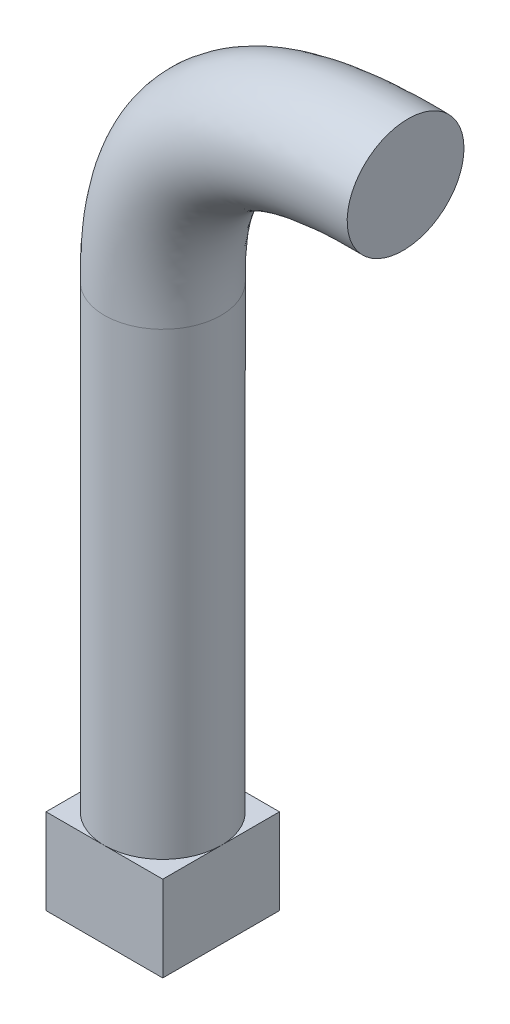
SolidWorks part; units mm, degrees
ref_plane "Front Plane" through (0, 0, 0) normal (0, 0, 1) x (1, 0, 0)
ref_plane "Top Plane" through (0, 0, 0) normal (0, 1, 0) x (1, 0, 0)
ref_plane "Right Plane" through (0, 0, 0) normal (1, 0, 0) x (0, 0, -1)
sketch "Sketch1" plane through (0, 0, 0) normal (0, 1, 0) x (1, 0, 0)
  line L1 (-7.5, 7.5) -> (7.5, 7.5)
  line L2 (-7.5, 7.5) -> (-7.5, -7.5)
  line L3 (-7.5, -7.5) -> (7.5, -7.5)
  line L4 (7.5, 7.5) -> (7.5, -7.5)
  line L5 (-7.5, 7.5) -> (7.5, -7.5) construction
  line L6 (-7.5, -7.5) -> (7.5, 7.5) construction
  point P0 (0, 0)
extrude "Boss-Extrude1" add sketch "Sketch1" along normal blind 11
sketch "Sketch2" plane through (0, 11, 0) normal (0, 1, 0) x (1, 0, 0)
  circle A0 centre (0, 0) radius 7.5
extrude "Boss-Extrude2" add sketch "Sketch2" along normal blind 59
sketch "Sketch3" plane through (0, 0, 0) normal (0, 0, 1) x (1, 0, 0)
  line L0 (7.5, 70) -> (-7.5, 70) construction
  spline S0 degree 2 poles (0, 70) (-0.5177, 97.1377) (31.2055, 96.4008) knots 0 0 0 1 1 1
  point P2 (2.572, 80.8507)
  point P4 (14.6542, 84.2003)
  point P5 (17.6449, 84.4395)
  point P8 (18.9608, 85.6358)
  point P9 (19.5008, 86.3332)
  point P10 (3.0646, 82.0529)
  point P11 (20.1067, 88.8893)
  point P12 (34.1622, 94.2121)
  point P13 (35.1619, 94.3532)
  point P14 (4.5681, 87.4202)
  point P15 (2.727, 86.021)
  point P16 (26.5323, 98.0521)
  point P17 (26.5683, 97.7919)
  point P18 (30.9658, 99.4161)
  point P19 (3.6143, 85.6256)
  point P20 (31.0436, 96.9173)
  point P21 (31.2055, 96.4008)
sketch "Sketch10" plane through (0, 70, 0) normal (0, 1, 0) x (1, 0, 0)
  circle A0 centre (0, 0) radius 7.5
sweep "Sweep2" add profiles "Sketch10" path "Sketch3"
